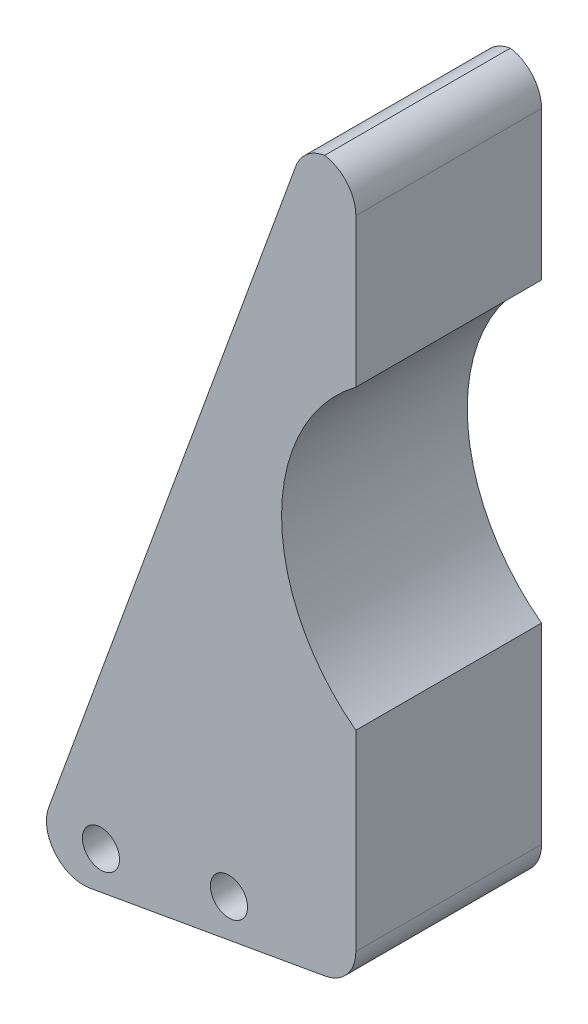
SolidWorks part; units mm, degrees
ref_plane "Front Plane" through (0, 0, 0) normal (0, 0, 1) x (1, 0, 0)
ref_plane "Top Plane" through (0, 0, 0) normal (0, 1, 0) x (1, 0, 0)
ref_plane "Right Plane" through (0, 0, 0) normal (1, 0, 0) x (0, 0, -1)
sketch "Sketch1" plane through (0, 0, 0) normal (0, 0, 1) x (1, 0, 0)
  line L0 (0, 0) -> (0, 60)
  line L1 (0, 190) -> (-13.7901, 190)
  line L2 (-13.7901, 190) -> (-88.6327, -15.6283)
  line L3 (-88.6327, -15.6283) -> (0, 0)
  line L4 (0, 140) -> (0, 190)
  arc A0 (0, 140) -> (0, 60) centre (30, 100) ccw
  circle A1 centre (-68.6327, -1.9475) radius 5
  circle A2 centre (-34.1644, 4.1302) radius 5
  dimension "D4" = 100
  dimension "D8" = 10
  dimension "D9" = 10
  dimension "D11" = 10
  dimension "D1" = 60
  dimension "D2" = 100
  dimension "D3" = 90
  dimension "D5" = 30
  dimension "D6" = 90
  dimension "D7" = 190
  dimension "D10" = 20
  dimension "D12" = 35
  dimension "D13" = 10
extrude "Boss-Extrude1" add sketch "Sketch1" along normal blind 50
fillet "Fillet2" radius 10 4 edges at (0, 0, 25) (-88.6327, -15.6283, 25) (-13.7901, 190, 25) (0, 190, 25)
ref_plane "Plane1" through (0, 0, 25) normal (0, 0, 1) x (1, 0, 0)
sketch "Sketch2" plane through (0, 0, 25) normal (0, 0, 1) x (1, 0, 0)
  circle A0 centre (-68.6327, -1.9475) radius 12.5
  dimension "D1" = 25
extrude "Cut-Extrude2" cut sketch "Sketch2" against normal mid plane 20
